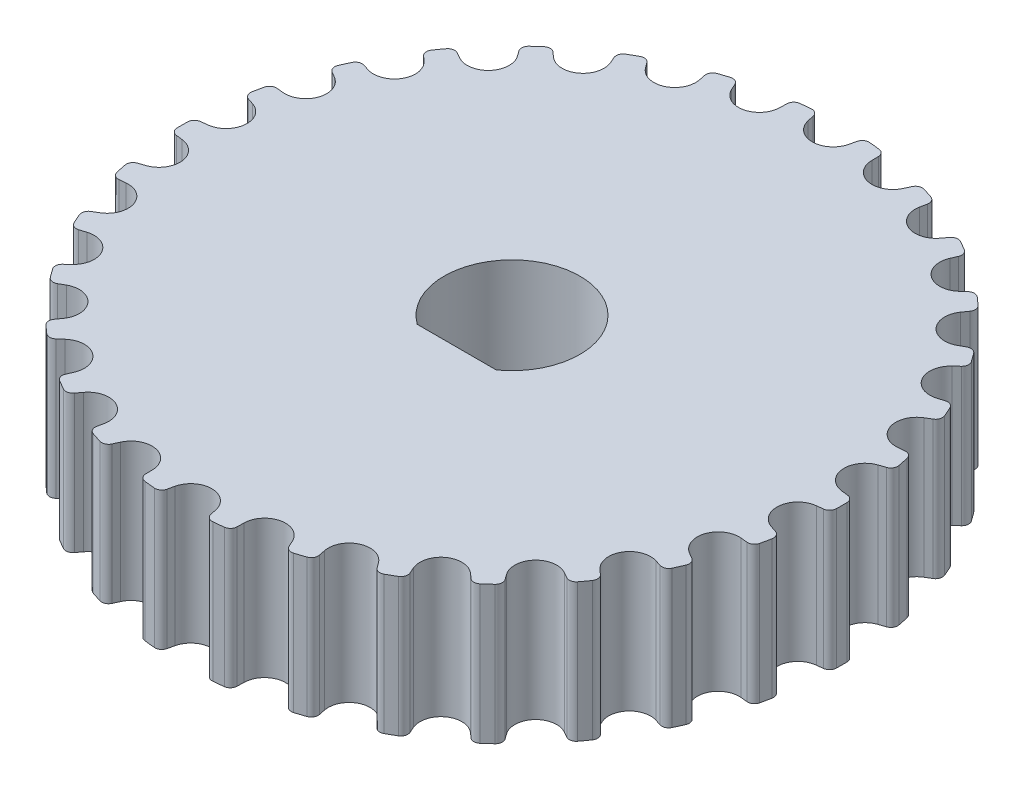
SolidWorks part; units mm, degrees
material "Acrylic (Medium-high impact)"
ref_plane "Front Plane" through (0, 0, 0) normal (0, 0, 1) x (1, 0, 0)
ref_plane "Top Plane" through (0, 0, 0) normal (0, 1, 0) x (1, 0, 0)
ref_plane "Right Plane" through (0, 0, 0) normal (1, 0, 0) x (0, 0, -1)
sketch "Sketch1" plane through (0, 0, 0) normal (0, 1, 0) x (1, 0, 0)
  circle A0 centre (0, 0) radius 14.3239
  dimension "D1" = 28.6479
extrude "Boss-Extrude1" add sketch "Sketch1" along normal blind 6
sketch "Sketch2" plane through (0, 6, 0) normal (0, 1, 0) x (1, 0, 0)
  line L0 (0, 0) -> (0, 14.3239) construction
  line L1 (-0.8883, 13.7564) -> (-0.95, 14.0339)
  line L2 (-2.9781, 14.0109) -> (-2.9781, 14.3239)
  line L3 (-2.9781, 14.3239) -> (2.9781, 14.3239)
  line L4 (0.8883, 13.7564) -> (0.95, 14.0339)
  line L5 (2.9781, 14.0109) -> (2.9781, 14.3239)
  circle A0 centre (0, 0) radius 14.3239 construction
  arc A1 (0.8883, 13.7564) -> (-0.8883, 13.7564) centre (0, 13.9539) cw
  arc A2 (-0.95, 14.0339) -> (-1.2694, 14.2676) centre (-1.2428, 13.9688) ccw
  arc A4 (0.95, 14.0339) -> (1.2694, 14.2676) centre (1.2428, 13.9688) cw
  arc A5 (-1.2694, 14.2676) -> (-2.9781, 14.0109) centre (0, 0) ccw
  arc A6 (1.2694, 14.2676) -> (2.9781, 14.0109) centre (0, 0) cw
  point P11 (0, 14.3239)
  point P19 (0, 13.0439)
  dimension "D3" = 0.3
  dimension "D5" = 0.91
  dimension "D2" = 0.95
  dimension "D4" = 1.28
  dimension "D6" = 12
extrude "Cut-Extrude1" cut sketch "Sketch2" against normal through all
pattern_circular "CirPattern1" count 30 over 360 about axis through (0, 6, 0) along (0, -1, 0) of "Cut-Extrude1"
sketch "Sketch3" plane through (0, 0, 0) normal (0, -1, 0) x (1, 0, 0)
  line L0 (1.7154, 2.4) -> (-1.7154, 2.4)
  arc A0 (-1.7154, 2.4) -> (1.7154, 2.4) centre (0, 0) ccw
  dimension "D1" = 5.9
  dimension "D2" = 2.4
extrude "Cut-Extrude2" cut sketch "Sketch3" against normal through all
sketch "Sketch5" plane through (0, 0, 0) normal (0, -1, 0) x (1, 0, 0)
  line L60 (6.3264, -12.2653) -> (6.4956, -12.4937)
  line L61 (7.5721, -11.8722) -> (7.4589, -11.6115)
  line L62 (8.7383, -10.682) -> (8.9513, -10.8702)
  line L63 (9.875, -10.0385) -> (9.7101, -9.807)
  line L64 (10.7682, -8.6318) -> (11.0157, -8.7716)
  line L65 (11.7463, -7.766) -> (11.5369, -7.5738)
  line L66 (12.3276, -6.2043) -> (12.5987, -6.2896)
  line L67 (13.1043, -5.1541) -> (12.8594, -5.0097)
  line L68 (13.3481, -3.5057) -> (13.6311, -3.5327)
  line L69 (13.8895, -2.3169) -> (13.62, -2.2266)
  line L70 (13.7853, -0.6538) -> (14.0677, -0.6215)
  line L71 (14.0677, 0.6215) -> (13.7853, 0.6538)
  line L72 (13.62, 2.2266) -> (13.8895, 2.3169)
  line L73 (13.6311, 3.5327) -> (13.3481, 3.5057)
  line L74 (12.8594, 5.0097) -> (13.1043, 5.1541)
  line L75 (12.5987, 6.2896) -> (12.3276, 6.2043)
  line L76 (11.5369, 7.5738) -> (11.7463, 7.766)
  line L77 (11.0157, 8.7716) -> (10.7682, 8.6318)
  line L78 (9.7101, 9.807) -> (9.875, 10.0385)
  line L79 (8.9513, 10.8702) -> (8.7383, 10.682)
  line L80 (7.4589, 11.6115) -> (7.5721, 11.8722)
  line L81 (6.4956, 12.4937) -> (6.3264, 12.2653)
  line L82 (4.8817, 12.9085) -> (4.9382, 13.1871)
  line L83 (3.7561, 13.5712) -> (3.638, 13.3126)
  line L84 (2.0912, 13.6414) -> (2.0886, 13.9257)
  line L85 (-0.8524, -14.0556) -> (-0.7907, -13.7781)
  line L86 (0.7907, -13.7781) -> (0.8524, -14.0556)
  line L87 (2.0886, -13.9257) -> (2.0912, -13.6414)
  line L88 (3.638, -13.3126) -> (3.7561, -13.5712)
  line L89 (4.9382, -13.1871) -> (4.8817, -12.9085)
  line L90 (6.3264, -12.2653) -> (6.4956, -12.4937)
  line L91 (7.5721, -11.8722) -> (7.4589, -11.6115)
  line L92 (8.7383, -10.682) -> (8.9513, -10.8702)
  line L93 (9.875, -10.0385) -> (9.7101, -9.807)
  line L94 (10.7682, -8.6318) -> (11.0157, -8.7716)
  line L95 (11.7463, -7.766) -> (11.5369, -7.5738)
  line L96 (12.3276, -6.2043) -> (12.5987, -6.2896)
  line L97 (13.1043, -5.1541) -> (12.8594, -5.0097)
  line L98 (13.3481, -3.5057) -> (13.6311, -3.5327)
  line L99 (13.8895, -2.3169) -> (13.62, -2.2266)
  line L100 (13.7853, -0.6538) -> (14.0677, -0.6215)
  line L101 (14.0677, 0.6215) -> (13.7853, 0.6538)
  line L102 (13.62, 2.2266) -> (13.8895, 2.3169)
  line L103 (13.6311, 3.5327) -> (13.3481, 3.5057)
  line L104 (12.8594, 5.0097) -> (13.1043, 5.1541)
  line L105 (12.5987, 6.2896) -> (12.3276, 6.2043)
  line L106 (11.5369, 7.5738) -> (11.7463, 7.766)
  line L107 (11.0157, 8.7716) -> (10.7682, 8.6318)
  line L108 (9.7101, 9.807) -> (9.875, 10.0385)
  line L109 (8.9513, 10.8702) -> (8.7383, 10.682)
  line L110 (7.4589, 11.6115) -> (7.5721, 11.8722)
  line L111 (6.4956, 12.4937) -> (6.3264, 12.2653)
  line L112 (4.8817, 12.9085) -> (4.9382, 13.1871)
  line L113 (3.7561, 13.5712) -> (3.638, 13.3126)
  line L114 (2.0912, 13.6414) -> (2.0886, 13.9257)
  line L115 (-0.8524, -14.0556) -> (-0.7907, -13.7781)
  line L116 (0.7907, -13.7781) -> (0.8524, -14.0556)
  line L117 (2.0886, -13.9257) -> (2.0912, -13.6414)
  line L118 (3.638, -13.3126) -> (3.7561, -13.5712)
  line L119 (4.9382, -13.1871) -> (4.8817, -12.9085)
  line L120 (0.8524, 14.0556) -> (0.7907, 13.7781)
  line L121 (0.8524, 14.0556) -> (0.7907, 13.7781)
  line L122 (-0.7907, 13.7781) -> (-0.8524, 14.0556)
  line L123 (-0.7907, 13.7781) -> (-0.8524, 14.0556)
  line L124 (-2.0886, 13.9257) -> (-2.0912, 13.6414)
  line L125 (-2.0886, 13.9257) -> (-2.0912, 13.6414)
  line L126 (-3.638, 13.3126) -> (-3.7561, 13.5712)
  line L127 (-3.638, 13.3126) -> (-3.7561, 13.5712)
  line L128 (-4.9382, 13.1871) -> (-4.8817, 12.9085)
  line L129 (-4.9382, 13.1871) -> (-4.8817, 12.9085)
  line L130 (-6.3264, 12.2653) -> (-6.4956, 12.4937)
  line L131 (-6.3264, 12.2653) -> (-6.4956, 12.4937)
  line L132 (-7.5721, 11.8722) -> (-7.4589, 11.6115)
  line L133 (-7.5721, 11.8722) -> (-7.4589, 11.6115)
  line L134 (-8.7383, 10.682) -> (-8.9513, 10.8702)
  line L135 (-8.7383, 10.682) -> (-8.9513, 10.8702)
  line L136 (-9.875, 10.0385) -> (-9.7101, 9.807)
  line L137 (-9.875, 10.0385) -> (-9.7101, 9.807)
  line L138 (-10.7682, 8.6318) -> (-11.0157, 8.7716)
  line L139 (-10.7682, 8.6318) -> (-11.0157, 8.7716)
  line L140 (-11.7463, 7.766) -> (-11.5369, 7.5738)
  line L141 (-11.7463, 7.766) -> (-11.5369, 7.5738)
  line L142 (-12.3276, 6.2043) -> (-12.5987, 6.2896)
  line L143 (-12.3276, 6.2043) -> (-12.5987, 6.2896)
  line L144 (-13.1043, 5.1541) -> (-12.8594, 5.0097)
  line L145 (-13.1043, 5.1541) -> (-12.8594, 5.0097)
  line L146 (-13.3481, 3.5057) -> (-13.6311, 3.5327)
  line L147 (-13.3481, 3.5057) -> (-13.6311, 3.5327)
  line L148 (-13.8895, 2.3169) -> (-13.62, 2.2266)
  line L149 (-13.8895, 2.3169) -> (-13.62, 2.2266)
  line L150 (-13.7853, 0.6538) -> (-14.0677, 0.6215)
  line L151 (-13.7853, 0.6538) -> (-14.0677, 0.6215)
  line L152 (-14.0677, -0.6215) -> (-13.7853, -0.6538)
  line L153 (-14.0677, -0.6215) -> (-13.7853, -0.6538)
  line L154 (-13.62, -2.2266) -> (-13.8895, -2.3169)
  line L155 (-13.62, -2.2266) -> (-13.8895, -2.3169)
  line L156 (-13.6311, -3.5327) -> (-13.3481, -3.5057)
  line L157 (-13.6311, -3.5327) -> (-13.3481, -3.5057)
  line L158 (-12.8594, -5.0097) -> (-13.1043, -5.1541)
  line L159 (-12.8594, -5.0097) -> (-13.1043, -5.1541)
  line L160 (-12.5987, -6.2896) -> (-12.3276, -6.2043)
  line L161 (-12.5987, -6.2896) -> (-12.3276, -6.2043)
  line L162 (-11.5369, -7.5738) -> (-11.7463, -7.766)
  line L163 (-11.5369, -7.5738) -> (-11.7463, -7.766)
  line L164 (-11.0157, -8.7716) -> (-10.7682, -8.6318)
  line L165 (-11.0157, -8.7716) -> (-10.7682, -8.6318)
  line L166 (-9.7101, -9.807) -> (-9.875, -10.0385)
  line L167 (-9.7101, -9.807) -> (-9.875, -10.0385)
  line L168 (-8.9513, -10.8702) -> (-8.7383, -10.682)
  line L169 (-8.9513, -10.8702) -> (-8.7383, -10.682)
  line L170 (-7.4589, -11.6115) -> (-7.5721, -11.8722)
  line L171 (-7.4589, -11.6115) -> (-7.5721, -11.8722)
  line L172 (-6.4956, -12.4937) -> (-6.3264, -12.2653)
  line L173 (-6.4956, -12.4937) -> (-6.3264, -12.2653)
  line L174 (-4.8817, -12.9085) -> (-4.9382, -13.1871)
  line L175 (-4.8817, -12.9085) -> (-4.9382, -13.1871)
  line L176 (-3.7561, -13.5712) -> (-3.638, -13.3126)
  line L177 (-3.7561, -13.5712) -> (-3.638, -13.3126)
  line L178 (-2.0912, -13.6414) -> (-2.0886, -13.9257)
  line L179 (-2.0912, -13.6414) -> (-2.0886, -13.9257)
  circle A60 centre (0, 0) radius 3.9038
  arc A120 (6.4956, -12.4937) -> (7.0114, -12.6052) centre (6.817, -12.2556) ccw
  arc A121 (7.0114, -12.6052) -> (7.4107, -12.3747) centre (0, 0) ccw
  arc A122 (7.4107, -12.3747) -> (7.5721, -11.8722) centre (7.2051, -12.0315) ccw
  arc A123 (8.7383, -10.682) -> (7.4589, -11.6115) centre (8.2019, -11.289) ccw
  arc A124 (8.9513, -10.8702) -> (9.479, -10.8719) centre (9.2161, -10.5704) ccw
  arc A125 (9.479, -10.8719) -> (9.8216, -10.5635) centre (0, 0) ccw
  arc A126 (9.8216, -10.5635) -> (9.875, -10.0385) centre (9.5492, -10.2705) ccw
  arc A127 (10.7682, -8.6318) -> (9.7101, -9.807) centre (10.3698, -9.337) ccw
  arc A128 (11.0157, -8.7716) -> (11.5323, -8.6636) centre (11.2124, -8.4233) ccw
  arc A129 (11.5323, -8.6636) -> (11.8032, -8.2906) centre (0, 0) ccw
  arc A130 (11.8032, -8.2906) -> (11.7463, -7.766) centre (11.4759, -8.0607) ccw
  arc A131 (12.3276, -6.2043) -> (11.5369, -7.5738) centre (12.0845, -6.977) ccw
  arc A132 (12.5987, -6.2896) -> (13.0815, -6.0766) centre (12.7187, -5.908) ccw
  arc A133 (13.0815, -6.0766) -> (13.269, -5.6554) centre (0, 0) ccw
  arc A134 (13.269, -5.6554) -> (13.1043, -5.1541) centre (12.901, -5.4986) ccw
  arc A135 (13.3481, -3.5057) -> (12.8594, -5.0097) centre (13.271, -4.312) ccw
  arc A136 (13.6311, -3.5327) -> (14.059, -3.224) centre (13.6691, -3.1346) ccw
  arc A137 (14.059, -3.224) -> (14.1549, -2.7731) centre (0, 0) ccw
  arc A138 (14.1549, -2.7731) -> (13.8895, -2.3169) centre (13.7623, -2.6962) ccw
  arc A139 (13.7853, -0.6538) -> (13.62, -2.2266) centre (13.8775, -1.4586) ccw
  arc A140 (14.0677, -0.6215) -> (14.4221, -0.2305) centre (14.0222, -0.2241) ccw
  arc A141 (14.4221, -0.2305) -> (14.4221, 0.2305) centre (0, 0) ccw
  arc A142 (14.4221, 0.2305) -> (14.0677, 0.6215) centre (14.0222, 0.2241) ccw
  arc A143 (13.62, 2.2266) -> (13.7853, 0.6538) centre (13.8775, 1.4586) ccw
  arc A144 (13.8895, 2.3169) -> (14.1549, 2.7731) centre (13.7623, 2.6962) ccw
  arc A145 (14.1549, 2.7731) -> (14.059, 3.224) centre (0, 0) ccw
  arc A146 (14.059, 3.224) -> (13.6311, 3.5327) centre (13.6691, 3.1346) ccw
  arc A147 (12.8594, 5.0097) -> (13.3481, 3.5057) centre (13.271, 4.312) ccw
  arc A148 (13.1043, 5.1541) -> (13.269, 5.6554) centre (12.901, 5.4986) ccw
  arc A149 (13.269, 5.6554) -> (13.0815, 6.0766) centre (0, 0) ccw
  arc A150 (13.0815, 6.0766) -> (12.5987, 6.2896) centre (12.7187, 5.908) ccw
  arc A151 (11.5369, 7.5738) -> (12.3276, 6.2043) centre (12.0845, 6.977) ccw
  arc A152 (11.7463, 7.766) -> (11.8032, 8.2906) centre (11.4759, 8.0607) ccw
  arc A153 (11.8032, 8.2906) -> (11.5323, 8.6636) centre (0, 0) ccw
  arc A154 (11.5323, 8.6636) -> (11.0157, 8.7716) centre (11.2124, 8.4233) ccw
  arc A155 (9.7101, 9.807) -> (10.7682, 8.6318) centre (10.3698, 9.337) ccw
  arc A156 (9.875, 10.0385) -> (9.8216, 10.5635) centre (9.5492, 10.2705) ccw
  arc A157 (9.8216, 10.5635) -> (9.479, 10.8719) centre (0, 0) ccw
  arc A158 (9.479, 10.8719) -> (8.9513, 10.8702) centre (9.2161, 10.5704) ccw
  arc A159 (7.4589, 11.6115) -> (8.7383, 10.682) centre (8.2019, 11.289) ccw
  arc A160 (7.5721, 11.8722) -> (7.4107, 12.3747) centre (7.2051, 12.0315) ccw
  arc A161 (7.4107, 12.3747) -> (7.0114, 12.6052) centre (0, 0) ccw
  arc A162 (7.0114, 12.6052) -> (6.4956, 12.4937) centre (6.817, 12.2556) ccw
  arc A163 (4.8817, 12.9085) -> (6.3264, 12.2653) centre (5.6756, 12.7476) ccw
  arc A164 (4.9382, 13.1871) -> (4.6759, 13.645) centre (4.5462, 13.2666) ccw
  arc A165 (4.6759, 13.645) -> (4.2375, 13.7875) centre (0, 0) ccw
  arc A166 (4.2375, 13.7875) -> (3.7561, 13.5712) centre (4.12, 13.4051) ccw
  arc A167 (2.0912, 13.6414) -> (3.638, 13.3126) centre (2.9012, 13.649) ccw
  arc A168 (2.0886, 13.9257) -> (1.7367, 14.319) centre (1.6886, 13.9219) ccw
  arc A169 (1.7367, 14.319) -> (1.2783, 14.3672) centre (0, 0) ccw
  arc A170 (-1.2783, -14.3672) -> (-0.8524, -14.0556) centre (-1.2428, -13.9688) ccw
  arc A171 (0.7907, -13.7781) -> (-0.7907, -13.7781) centre (0, -13.9539) ccw
  arc A172 (0.8524, -14.0556) -> (1.2783, -14.3672) centre (1.2428, -13.9688) ccw
  arc A173 (1.2783, -14.3672) -> (1.7367, -14.319) centre (0, 0) ccw
  arc A174 (1.7367, -14.319) -> (2.0886, -13.9257) centre (1.6886, -13.9219) ccw
  arc A175 (3.638, -13.3126) -> (2.0912, -13.6414) centre (2.9012, -13.649) ccw
  arc A176 (3.7561, -13.5712) -> (4.2375, -13.7875) centre (4.12, -13.4051) ccw
  arc A177 (4.2375, -13.7875) -> (4.6759, -13.645) centre (0, 0) ccw
  arc A178 (4.6759, -13.645) -> (4.9382, -13.1871) centre (4.5462, -13.2666) ccw
  arc A179 (6.3264, -12.2653) -> (4.8817, -12.9085) centre (5.6756, -12.7476) ccw
  arc A180 (6.4956, -12.4937) -> (7.0114, -12.6052) centre (6.817, -12.2556) ccw
  arc A181 (7.0114, -12.6052) -> (7.4107, -12.3747) centre (0, 0) ccw
  arc A182 (7.4107, -12.3747) -> (7.5721, -11.8722) centre (7.2051, -12.0315) ccw
  arc A183 (8.7383, -10.682) -> (7.4589, -11.6115) centre (8.2019, -11.289) ccw
  arc A184 (8.9513, -10.8702) -> (9.479, -10.8719) centre (9.2161, -10.5704) ccw
  arc A185 (9.479, -10.8719) -> (9.8216, -10.5635) centre (0, 0) ccw
  arc A186 (9.8216, -10.5635) -> (9.875, -10.0385) centre (9.5492, -10.2705) ccw
  arc A187 (10.7682, -8.6318) -> (9.7101, -9.807) centre (10.3698, -9.337) ccw
  arc A188 (11.0157, -8.7716) -> (11.5323, -8.6636) centre (11.2124, -8.4233) ccw
  arc A189 (11.5323, -8.6636) -> (11.8032, -8.2906) centre (0, 0) ccw
  arc A190 (11.8032, -8.2906) -> (11.7463, -7.766) centre (11.4759, -8.0607) ccw
  arc A191 (12.3276, -6.2043) -> (11.5369, -7.5738) centre (12.0845, -6.977) ccw
  arc A192 (12.5987, -6.2896) -> (13.0815, -6.0766) centre (12.7187, -5.908) ccw
  arc A193 (13.0815, -6.0766) -> (13.269, -5.6554) centre (0, 0) ccw
  arc A194 (13.269, -5.6554) -> (13.1043, -5.1541) centre (12.901, -5.4986) ccw
  arc A195 (13.3481, -3.5057) -> (12.8594, -5.0097) centre (13.271, -4.312) ccw
  arc A196 (13.6311, -3.5327) -> (14.059, -3.224) centre (13.6691, -3.1346) ccw
  arc A197 (14.059, -3.224) -> (14.1549, -2.7731) centre (0, 0) ccw
  arc A198 (14.1549, -2.7731) -> (13.8895, -2.3169) centre (13.7623, -2.6962) ccw
  arc A199 (13.7853, -0.6538) -> (13.62, -2.2266) centre (13.8775, -1.4586) ccw
  arc A200 (14.0677, -0.6215) -> (14.4221, -0.2305) centre (14.0222, -0.2241) ccw
  arc A201 (14.4221, -0.2305) -> (14.4221, 0.2305) centre (0, 0) ccw
  arc A202 (14.4221, 0.2305) -> (14.0677, 0.6215) centre (14.0222, 0.2241) ccw
  arc A203 (13.62, 2.2266) -> (13.7853, 0.6538) centre (13.8775, 1.4586) ccw
  arc A204 (13.8895, 2.3169) -> (14.1549, 2.7731) centre (13.7623, 2.6962) ccw
  arc A205 (14.1549, 2.7731) -> (14.059, 3.224) centre (0, 0) ccw
  arc A206 (14.059, 3.224) -> (13.6311, 3.5327) centre (13.6691, 3.1346) ccw
  arc A207 (12.8594, 5.0097) -> (13.3481, 3.5057) centre (13.271, 4.312) ccw
  arc A208 (13.1043, 5.1541) -> (13.269, 5.6554) centre (12.901, 5.4986) ccw
  arc A209 (13.269, 5.6554) -> (13.0815, 6.0766) centre (0, 0) ccw
  arc A210 (13.0815, 6.0766) -> (12.5987, 6.2896) centre (12.7187, 5.908) ccw
  arc A211 (11.5369, 7.5738) -> (12.3276, 6.2043) centre (12.0845, 6.977) ccw
  arc A212 (11.7463, 7.766) -> (11.8032, 8.2906) centre (11.4759, 8.0607) ccw
  arc A213 (11.8032, 8.2906) -> (11.5323, 8.6636) centre (0, 0) ccw
  arc A214 (11.5323, 8.6636) -> (11.0157, 8.7716) centre (11.2124, 8.4233) ccw
  arc A215 (9.7101, 9.807) -> (10.7682, 8.6318) centre (10.3698, 9.337) ccw
  arc A216 (9.875, 10.0385) -> (9.8216, 10.5635) centre (9.5492, 10.2705) ccw
  arc A217 (9.8216, 10.5635) -> (9.479, 10.8719) centre (0, 0) ccw
  arc A218 (9.479, 10.8719) -> (8.9513, 10.8702) centre (9.2161, 10.5704) ccw
  arc A219 (7.4589, 11.6115) -> (8.7383, 10.682) centre (8.2019, 11.289) ccw
  arc A220 (7.5721, 11.8722) -> (7.4107, 12.3747) centre (7.2051, 12.0315) ccw
  arc A221 (7.4107, 12.3747) -> (7.0114, 12.6052) centre (0, 0) ccw
  arc A222 (7.0114, 12.6052) -> (6.4956, 12.4937) centre (6.817, 12.2556) ccw
  arc A223 (4.8817, 12.9085) -> (6.3264, 12.2653) centre (5.6756, 12.7476) ccw
  arc A224 (4.9382, 13.1871) -> (4.6759, 13.645) centre (4.5462, 13.2666) ccw
  arc A225 (4.6759, 13.645) -> (4.2375, 13.7875) centre (0, 0) ccw
  arc A226 (4.2375, 13.7875) -> (3.7561, 13.5712) centre (4.12, 13.4051) ccw
  arc A227 (2.0912, 13.6414) -> (3.638, 13.3126) centre (2.9012, 13.649) ccw
  arc A228 (2.0886, 13.9257) -> (1.7367, 14.319) centre (1.6886, 13.9219) ccw
  arc A229 (1.7367, 14.319) -> (1.2783, 14.3672) centre (0, 0) ccw
  arc A230 (-1.2783, -14.3672) -> (-0.8524, -14.0556) centre (-1.2428, -13.9688) ccw
  arc A231 (0.7907, -13.7781) -> (-0.7907, -13.7781) centre (0, -13.9539) ccw
  arc A232 (0.8524, -14.0556) -> (1.2783, -14.3672) centre (1.2428, -13.9688) ccw
  arc A233 (1.2783, -14.3672) -> (1.7367, -14.319) centre (0, 0) ccw
  arc A234 (1.7367, -14.319) -> (2.0886, -13.9257) centre (1.6886, -13.9219) ccw
  arc A235 (3.638, -13.3126) -> (2.0912, -13.6414) centre (2.9012, -13.649) ccw
  arc A236 (3.7561, -13.5712) -> (4.2375, -13.7875) centre (4.12, -13.4051) ccw
  arc A237 (4.2375, -13.7875) -> (4.6759, -13.645) centre (0, 0) ccw
  arc A238 (4.6759, -13.645) -> (4.9382, -13.1871) centre (4.5462, -13.2666) ccw
  arc A239 (6.3264, -12.2653) -> (4.8817, -12.9085) centre (5.6756, -12.7476) ccw
  arc A241 (1.2783, 14.3672) -> (0.8524, 14.0556) centre (1.2428, 13.9688) ccw
  arc A242 (1.2783, 14.3672) -> (0.8524, 14.0556) centre (1.2428, 13.9688) ccw
  arc A243 (-0.7907, 13.7781) -> (0.7907, 13.7781) centre (0, 13.9539) ccw
  arc A244 (-0.7907, 13.7781) -> (0.7907, 13.7781) centre (0, 13.9539) ccw
  arc A245 (-0.8524, 14.0556) -> (-1.2783, 14.3672) centre (-1.2428, 13.9688) ccw
  arc A246 (-0.8524, 14.0556) -> (-1.2783, 14.3672) centre (-1.2428, 13.9688) ccw
  arc A247 (-1.2783, 14.3672) -> (-1.7367, 14.319) centre (0, 0) ccw
  arc A248 (-1.2783, 14.3672) -> (-1.7367, 14.319) centre (0, 0) ccw
  arc A249 (-1.7367, 14.319) -> (-2.0886, 13.9257) centre (-1.6886, 13.9219) ccw
  arc A250 (-1.7367, 14.319) -> (-2.0886, 13.9257) centre (-1.6886, 13.9219) ccw
  arc A251 (-3.638, 13.3126) -> (-2.0912, 13.6414) centre (-2.9012, 13.649) ccw
  arc A252 (-3.638, 13.3126) -> (-2.0912, 13.6414) centre (-2.9012, 13.649) ccw
  arc A253 (-3.7561, 13.5712) -> (-4.2375, 13.7875) centre (-4.12, 13.4051) ccw
  arc A254 (-3.7561, 13.5712) -> (-4.2375, 13.7875) centre (-4.12, 13.4051) ccw
  arc A255 (-4.2375, 13.7875) -> (-4.6759, 13.645) centre (0, 0) ccw
  arc A256 (-4.2375, 13.7875) -> (-4.6759, 13.645) centre (0, 0) ccw
  arc A257 (-4.6759, 13.645) -> (-4.9382, 13.1871) centre (-4.5462, 13.2666) ccw
  arc A258 (-4.6759, 13.645) -> (-4.9382, 13.1871) centre (-4.5462, 13.2666) ccw
  arc A259 (-6.3264, 12.2653) -> (-4.8817, 12.9085) centre (-5.6756, 12.7476) ccw
  arc A260 (-6.3264, 12.2653) -> (-4.8817, 12.9085) centre (-5.6756, 12.7476) ccw
  arc A261 (-6.4956, 12.4937) -> (-7.0114, 12.6052) centre (-6.817, 12.2556) ccw
  arc A262 (-6.4956, 12.4937) -> (-7.0114, 12.6052) centre (-6.817, 12.2556) ccw
  arc A263 (-7.0114, 12.6052) -> (-7.4107, 12.3747) centre (0, 0) ccw
  arc A264 (-7.0114, 12.6052) -> (-7.4107, 12.3747) centre (0, 0) ccw
  arc A265 (-7.4107, 12.3747) -> (-7.5721, 11.8722) centre (-7.2051, 12.0315) ccw
  arc A266 (-7.4107, 12.3747) -> (-7.5721, 11.8722) centre (-7.2051, 12.0315) ccw
  arc A267 (-8.7383, 10.682) -> (-7.4589, 11.6115) centre (-8.2019, 11.289) ccw
  arc A268 (-8.7383, 10.682) -> (-7.4589, 11.6115) centre (-8.2019, 11.289) ccw
  arc A269 (-8.9513, 10.8702) -> (-9.479, 10.8719) centre (-9.2161, 10.5704) ccw
  arc A270 (-8.9513, 10.8702) -> (-9.479, 10.8719) centre (-9.2161, 10.5704) ccw
  arc A271 (-9.479, 10.8719) -> (-9.8216, 10.5635) centre (0, 0) ccw
  arc A272 (-9.479, 10.8719) -> (-9.8216, 10.5635) centre (0, 0) ccw
  arc A273 (-9.8216, 10.5635) -> (-9.875, 10.0385) centre (-9.5492, 10.2705) ccw
  arc A274 (-9.8216, 10.5635) -> (-9.875, 10.0385) centre (-9.5492, 10.2705) ccw
  arc A275 (-10.7682, 8.6318) -> (-9.7101, 9.807) centre (-10.3698, 9.337) ccw
  arc A276 (-10.7682, 8.6318) -> (-9.7101, 9.807) centre (-10.3698, 9.337) ccw
  arc A277 (-11.0157, 8.7716) -> (-11.5323, 8.6636) centre (-11.2124, 8.4233) ccw
  arc A278 (-11.0157, 8.7716) -> (-11.5323, 8.6636) centre (-11.2124, 8.4233) ccw
  arc A279 (-11.5323, 8.6636) -> (-11.8032, 8.2906) centre (0, 0) ccw
  arc A280 (-11.5323, 8.6636) -> (-11.8032, 8.2906) centre (0, 0) ccw
  arc A281 (-11.8032, 8.2906) -> (-11.7463, 7.766) centre (-11.4759, 8.0607) ccw
  arc A282 (-11.8032, 8.2906) -> (-11.7463, 7.766) centre (-11.4759, 8.0607) ccw
  arc A283 (-12.3276, 6.2043) -> (-11.5369, 7.5738) centre (-12.0845, 6.977) ccw
  arc A284 (-12.3276, 6.2043) -> (-11.5369, 7.5738) centre (-12.0845, 6.977) ccw
  arc A285 (-12.5987, 6.2896) -> (-13.0815, 6.0766) centre (-12.7187, 5.908) ccw
  arc A286 (-12.5987, 6.2896) -> (-13.0815, 6.0766) centre (-12.7187, 5.908) ccw
  arc A287 (-13.0815, 6.0766) -> (-13.269, 5.6554) centre (0, 0) ccw
  arc A288 (-13.0815, 6.0766) -> (-13.269, 5.6554) centre (0, 0) ccw
  arc A289 (-13.269, 5.6554) -> (-13.1043, 5.1541) centre (-12.901, 5.4986) ccw
  arc A290 (-13.269, 5.6554) -> (-13.1043, 5.1541) centre (-12.901, 5.4986) ccw
  arc A291 (-13.3481, 3.5057) -> (-12.8594, 5.0097) centre (-13.271, 4.312) ccw
  arc A292 (-13.3481, 3.5057) -> (-12.8594, 5.0097) centre (-13.271, 4.312) ccw
  arc A293 (-13.6311, 3.5327) -> (-14.059, 3.224) centre (-13.6691, 3.1346) ccw
  arc A294 (-13.6311, 3.5327) -> (-14.059, 3.224) centre (-13.6691, 3.1346) ccw
  arc A295 (-14.059, 3.224) -> (-14.1549, 2.7731) centre (0, 0) ccw
  arc A296 (-14.059, 3.224) -> (-14.1549, 2.7731) centre (0, 0) ccw
  arc A297 (-14.1549, 2.7731) -> (-13.8895, 2.3169) centre (-13.7623, 2.6962) ccw
  arc A298 (-14.1549, 2.7731) -> (-13.8895, 2.3169) centre (-13.7623, 2.6962) ccw
  arc A299 (-13.7853, 0.6538) -> (-13.62, 2.2266) centre (-13.8775, 1.4586) ccw
  arc A300 (-13.7853, 0.6538) -> (-13.62, 2.2266) centre (-13.8775, 1.4586) ccw
  arc A301 (-14.0677, 0.6215) -> (-14.4221, 0.2305) centre (-14.0222, 0.2241) ccw
  arc A302 (-14.0677, 0.6215) -> (-14.4221, 0.2305) centre (-14.0222, 0.2241) ccw
  arc A303 (-14.4221, 0.2305) -> (-14.4221, -0.2305) centre (0, 0) ccw
  arc A304 (-14.4221, 0.2305) -> (-14.4221, -0.2305) centre (0, 0) ccw
  arc A305 (-14.4221, -0.2305) -> (-14.0677, -0.6215) centre (-14.0222, -0.2241) ccw
  arc A306 (-14.4221, -0.2305) -> (-14.0677, -0.6215) centre (-14.0222, -0.2241) ccw
  arc A307 (-13.62, -2.2266) -> (-13.7853, -0.6538) centre (-13.8775, -1.4586) ccw
  arc A308 (-13.62, -2.2266) -> (-13.7853, -0.6538) centre (-13.8775, -1.4586) ccw
  arc A309 (-13.8895, -2.3169) -> (-14.1549, -2.7731) centre (-13.7623, -2.6962) ccw
  arc A310 (-13.8895, -2.3169) -> (-14.1549, -2.7731) centre (-13.7623, -2.6962) ccw
  arc A311 (-14.1549, -2.7731) -> (-14.059, -3.224) centre (0, 0) ccw
  arc A312 (-14.1549, -2.7731) -> (-14.059, -3.224) centre (0, 0) ccw
  arc A313 (-14.059, -3.224) -> (-13.6311, -3.5327) centre (-13.6691, -3.1346) ccw
  arc A314 (-14.059, -3.224) -> (-13.6311, -3.5327) centre (-13.6691, -3.1346) ccw
  arc A315 (-12.8594, -5.0097) -> (-13.3481, -3.5057) centre (-13.271, -4.312) ccw
  arc A316 (-12.8594, -5.0097) -> (-13.3481, -3.5057) centre (-13.271, -4.312) ccw
  arc A317 (-13.1043, -5.1541) -> (-13.269, -5.6554) centre (-12.901, -5.4986) ccw
  arc A318 (-13.1043, -5.1541) -> (-13.269, -5.6554) centre (-12.901, -5.4986) ccw
  arc A319 (-13.269, -5.6554) -> (-13.0815, -6.0766) centre (0, 0) ccw
  arc A320 (-13.269, -5.6554) -> (-13.0815, -6.0766) centre (0, 0) ccw
  arc A321 (-13.0815, -6.0766) -> (-12.5987, -6.2896) centre (-12.7187, -5.908) ccw
  arc A322 (-13.0815, -6.0766) -> (-12.5987, -6.2896) centre (-12.7187, -5.908) ccw
  arc A323 (-11.5369, -7.5738) -> (-12.3276, -6.2043) centre (-12.0845, -6.977) ccw
  arc A324 (-11.5369, -7.5738) -> (-12.3276, -6.2043) centre (-12.0845, -6.977) ccw
  arc A325 (-11.7463, -7.766) -> (-11.8032, -8.2906) centre (-11.4759, -8.0607) ccw
  arc A326 (-11.7463, -7.766) -> (-11.8032, -8.2906) centre (-11.4759, -8.0607) ccw
  arc A327 (-11.8032, -8.2906) -> (-11.5323, -8.6636) centre (0, 0) ccw
  arc A328 (-11.8032, -8.2906) -> (-11.5323, -8.6636) centre (0, 0) ccw
  arc A329 (-11.5323, -8.6636) -> (-11.0157, -8.7716) centre (-11.2124, -8.4233) ccw
  arc A330 (-11.5323, -8.6636) -> (-11.0157, -8.7716) centre (-11.2124, -8.4233) ccw
  arc A331 (-9.7101, -9.807) -> (-10.7682, -8.6318) centre (-10.3698, -9.337) ccw
  arc A332 (-9.7101, -9.807) -> (-10.7682, -8.6318) centre (-10.3698, -9.337) ccw
  arc A333 (-9.875, -10.0385) -> (-9.8216, -10.5635) centre (-9.5492, -10.2705) ccw
  arc A334 (-9.875, -10.0385) -> (-9.8216, -10.5635) centre (-9.5492, -10.2705) ccw
  arc A335 (-9.8216, -10.5635) -> (-9.479, -10.8719) centre (0, 0) ccw
  arc A336 (-9.8216, -10.5635) -> (-9.479, -10.8719) centre (0, 0) ccw
  arc A337 (-9.479, -10.8719) -> (-8.9513, -10.8702) centre (-9.2161, -10.5704) ccw
  arc A338 (-9.479, -10.8719) -> (-8.9513, -10.8702) centre (-9.2161, -10.5704) ccw
  arc A339 (-7.4589, -11.6115) -> (-8.7383, -10.682) centre (-8.2019, -11.289) ccw
  arc A340 (-7.4589, -11.6115) -> (-8.7383, -10.682) centre (-8.2019, -11.289) ccw
  arc A341 (-7.5721, -11.8722) -> (-7.4107, -12.3747) centre (-7.2051, -12.0315) ccw
  arc A342 (-7.5721, -11.8722) -> (-7.4107, -12.3747) centre (-7.2051, -12.0315) ccw
  arc A343 (-7.4107, -12.3747) -> (-7.0114, -12.6052) centre (0, 0) ccw
  arc A344 (-7.4107, -12.3747) -> (-7.0114, -12.6052) centre (0, 0) ccw
  arc A345 (-7.0114, -12.6052) -> (-6.4956, -12.4937) centre (-6.817, -12.2556) ccw
  arc A346 (-7.0114, -12.6052) -> (-6.4956, -12.4937) centre (-6.817, -12.2556) ccw
  arc A347 (-4.8817, -12.9085) -> (-6.3264, -12.2653) centre (-5.6756, -12.7476) ccw
  arc A348 (-4.8817, -12.9085) -> (-6.3264, -12.2653) centre (-5.6756, -12.7476) ccw
  arc A349 (-4.9382, -13.1871) -> (-4.6759, -13.645) centre (-4.5462, -13.2666) ccw
  arc A350 (-4.9382, -13.1871) -> (-4.6759, -13.645) centre (-4.5462, -13.2666) ccw
  arc A351 (-4.6759, -13.645) -> (-4.2375, -13.7875) centre (0, 0) ccw
  arc A352 (-4.6759, -13.645) -> (-4.2375, -13.7875) centre (0, 0) ccw
  arc A353 (-4.2375, -13.7875) -> (-3.7561, -13.5712) centre (-4.12, -13.4051) ccw
  arc A354 (-4.2375, -13.7875) -> (-3.7561, -13.5712) centre (-4.12, -13.4051) ccw
  arc A355 (-2.0912, -13.6414) -> (-3.638, -13.3126) centre (-2.9012, -13.649) ccw
  arc A356 (-2.0912, -13.6414) -> (-3.638, -13.3126) centre (-2.9012, -13.649) ccw
  arc A357 (-2.0886, -13.9257) -> (-1.7367, -14.319) centre (-1.6886, -13.9219) ccw
  arc A358 (-2.0886, -13.9257) -> (-1.7367, -14.319) centre (-1.6886, -13.9219) ccw
  arc A359 (-1.7367, -14.319) -> (-1.2783, -14.3672) centre (0, 0) ccw
  arc A360 (-1.7367, -14.319) -> (-1.2783, -14.3672) centre (0, 0) ccw
  dimension "D1" = 0.1
extrude "Boss-Extrude2" [suppressed] add sketch "Sketch5" against normal up to surface (5.8 mm away) up to face at (0, 6, -0.275)
sketch "Sketch6" plane through (0, 6, 0) normal (0, 1, 0) x (1, 0, 0)
  circle A0 centre (0, -10) radius 2.5
  dimension "D1" = 5
  dimension "D2" = 10
extrude "Cut-Extrude3" [suppressed] cut sketch "Sketch6" against normal through all
equation "\"smallPulleyTeeth\"= 30"
equation "\"largePulleyTeeth\"= 30"
equation "\"eighthThick\"= 3.0mm"
equation "\"D1@Sketch1\"=3*\"smallPulleyTeeth\"/pi"
equation "\"D1@Boss-Extrude1\" = \"eighthThick\" * 2"
equation "\"D6@Sketch2\"=360/\"smallPulleyTeeth\""
equation "\"quarterThick\"=6.0mm"
equation "\"D1@CirPattern1\"=\"smallPulleyTeeth\""
equation "\"sixteenthThick\" = 1.7mm"
equation "\"OD\" = 145mm"
equation "\"puckAngle\" = 60.5deg"
equation "\"puckDiam\" = 76.5mm"
equation "\"axlePress\" = 5.9mm"
equation "\"press\" = 0.2mm"
equation "\"wheelClear\" = 0.3mm"
equation "\"10-32clear\" = 4.8mm"
equation "\"6-32clear\" = 3.3mm"
equation "\"8-32clear\" = 4.0mm"
equation "\"wheelHeight\" = 22mm"
equation "\"D1@Sketch3\"=\"axlePress\""
